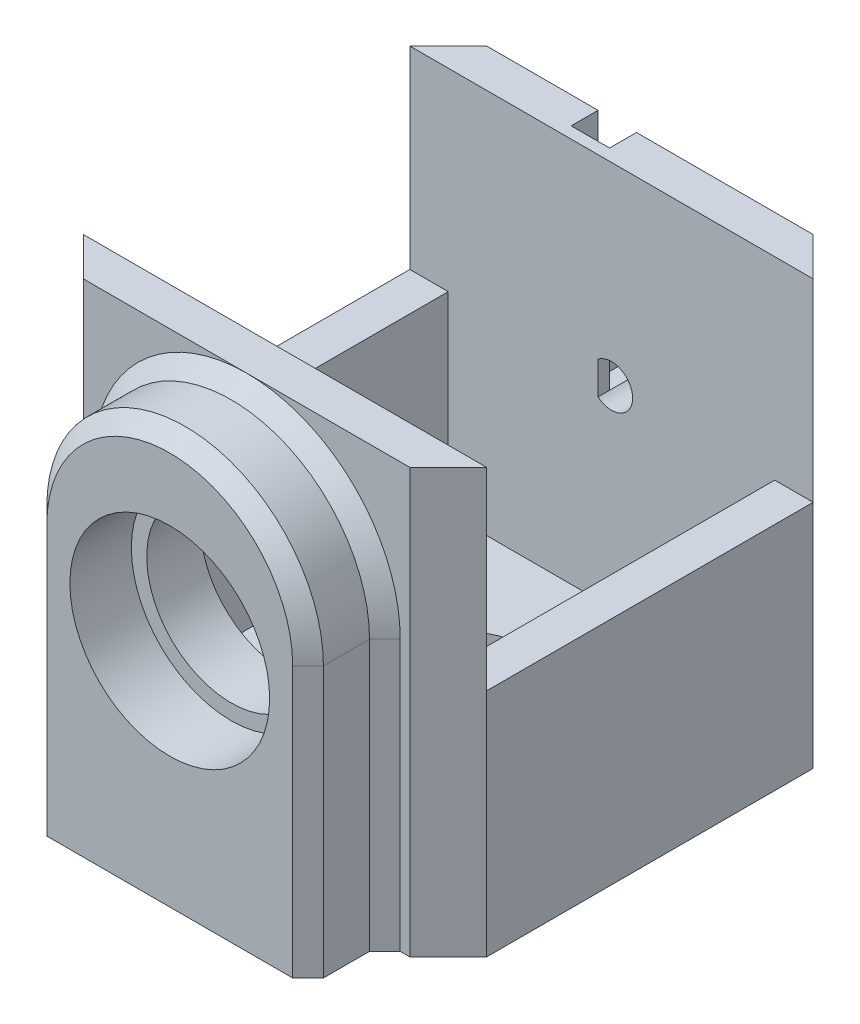
SolidWorks part; units mm, degrees
ref_plane "Front Plane" through (0, 0, 0) normal (0, 0, 1) x (1, 0, 0)
ref_plane "Top Plane" through (0, 0, 0) normal (0, 1, 0) x (1, 0, 0)
ref_plane "Right Plane" through (0, 0, 0) normal (1, 0, 0) x (0, 0, -1)
sketch "Sketch1" plane through (0, 0, 0) normal (0, 1, 0) x (1, 0, 0)
  line L0 (-26.25, 26.25) -> (-26.25, -26.25)
  line L1 (-21.25, 21.25) -> (21.25, 21.25)
  line L2 (-21.25, 21.25) -> (-21.25, -21.25)
  line L3 (-21.25, -21.25) -> (21.25, -21.25)
  line L4 (21.25, 21.25) -> (21.25, -21.25)
  line L5 (-21.25, 21.25) -> (21.25, -21.25) construction
  line L6 (-21.25, -21.25) -> (21.25, 21.25) construction
  line L7 (-26.25, -26.25) -> (26.25, -26.25)
  line L8 (26.25, 26.25) -> (26.25, -26.25)
  line L9 (-26.25, 26.25) -> (26.25, 26.25)
  point P0 (0, 0)
  dimension "D1" = 42.5
  dimension "D2" = 42.5
  dimension "D3" = 5
extrude "Boss-Extrude1" add sketch "Sketch1" along normal blind 60
sketch "Sketch2" plane through (0, 0, 0) normal (0, 1, 0) x (1, 0, 0)
  line L1 (-21.25, -21.25) -> (21.25, -21.25)
  line L2 (-21.25, -21.25) -> (-21.25, 21.25)
  line L3 (-21.25, 21.25) -> (21.25, 21.25)
  line L4 (21.25, -21.25) -> (21.25, 21.25)
  line L5 (-21.25, -21.25) -> (21.25, 21.25) construction
  line L6 (-21.25, 21.25) -> (21.25, -21.25) construction
  point P0 (0, 0)
extrude "Boss-Extrude2" add sketch "Sketch2" along normal blind 5
sketch "Sketch3" plane through (0, 5, 0) normal (0, 1, 0) x (1, 0, 0)
  line L0 (0, 21.25) -> (0, -21.25) construction
  line L1 (21.25, 21.25) -> (-21.25, 21.25) construction
  line L2 (-21.25, -21.25) -> (21.25, -21.25) construction
  line L3 (-21.25, 0) -> (21.25, 0) construction
  line L4 (-21.25, 21.25) -> (-21.25, -21.25) construction
  line L5 (21.25, -21.25) -> (21.25, 21.25) construction
  circle A0 centre (-15.5, 15.5) radius 1.75
  circle A1 centre (-15.5, -15.5) radius 1.75
  circle A2 centre (15.5, 15.5) radius 1.75
  circle A3 centre (15.5, -15.5) radius 1.75
  circle A4 centre (0, 0) radius 7.5
  dimension "D1" = 3.5
  dimension "D2" = 15
  dimension "D3" = 31
  dimension "D4" = 31
extrude "Cut-Extrude1" cut sketch "Sketch3" against normal through all both and the other way through all
sketch "Sketch4" plane through (0, 5, 0) normal (0, 1, 0) x (1, 0, 0)
  circle A0 centre (0, 0) radius 11.5
extrude "Cut-Extrude2" cut sketch "Sketch4" against normal blind 2
sketch "Sketch5" plane through (0, 0, -26.25) normal (0, 0, -1) x (-1, 0, 0)
  line L0 (0, 30) -> (0, -2.8991) construction
  line L1 (10, 30) -> (10, -2.8991)
  line L2 (-10, 30) -> (-10, -2.8991)
  line L3 (-26.25, 0) -> (26.25, 0) construction
  line L4 (0, 30) -> (26.25, 30) construction
  arc A0 (10, 30) -> (-10, 30) centre (0, 30) ccw
  arc A1 (-10, -2.8991) -> (10, -2.8991) centre (0, -2.8991) ccw
  circle A2 centre (-4, 37) radius 0.75
  circle A3 centre (0, 37) radius 0.75
  circle A4 centre (4, 37) radius 0.75
  circle A5 centre (-7, 34) radius 0.75
  circle A6 centre (-7, 30) radius 0.75
  circle A7 centre (-7, 26) radius 0.75
  circle A8 centre (-4, 23) radius 0.75
  circle A9 centre (0, 23) radius 0.75
  circle A10 centre (4, 23) radius 0.75
  circle A11 centre (7, 26) radius 0.75
  circle A12 centre (7, 30) radius 0.75
  circle A13 centre (7, 34) radius 0.75
  circle A14 centre (0, 30) radius 3.5
  point P3 (0, 13.5505)
  dimension "D1" = 10
  dimension "D3" = 1.5
  dimension "D6" = 4
  dimension "D10" = 7
  dimension "D2" = 30
  dimension "D4" = 4
  dimension "D5" = 4
  dimension "D7" = 4
  dimension "D8" = 7
  dimension "D9" = 7
extrude "Boss-Extrude3" add sketch "Sketch5" along normal blind 10
sketch "Sketch6" plane through (0, 0, -26.25) normal (0, 0, -1) x (-1, 0, 0)
  line L0 (-26.25, 0) -> (26.25, 0)
  line L1 (26.25, 0) -> (26.25, -16.2161)
  line L2 (26.25, -16.2161) -> (-26.25, -16.2161)
  line L3 (-26.25, -16.2161) -> (-26.25, 0)
extrude "Cut-Extrude3" cut sketch "Sketch6" against normal through all both and the other way through all
sketch "Sketch7" plane through (0, 0, -26.25) normal (0, 0, -1) x (-1, 0, 0)
  circle A0 centre (0, 30) radius 3.5
  circle A1 centre (-4, 37) radius 0.75
  circle A2 centre (0, 37) radius 0.75
  circle A3 centre (4, 37) radius 0.75
  circle A4 centre (7, 34) radius 0.75
  circle A5 centre (7, 30) radius 0.75
  circle A6 centre (7, 26) radius 0.75
  circle A7 centre (4, 23) radius 0.75
  circle A8 centre (0, 23) radius 0.75
  circle A9 centre (-4, 23) radius 0.75
  circle A10 centre (-7, 26) radius 0.75
  circle A11 centre (-7, 30) radius 0.75
  circle A12 centre (-7, 34) radius 0.75
  circle A13 centre (0, 37) radius 0.75 construction
  circle A14 centre (4, 37) radius 0.75 construction
  circle A15 centre (-4, 37) radius 0.75 construction
  circle A16 centre (-7, 34) radius 0.75 construction
  circle A17 centre (-7, 30) radius 0.75 construction
  circle A18 centre (-7, 26) radius 0.75 construction
  circle A19 centre (-4, 23) radius 0.75 construction
  circle A20 centre (0, 23) radius 0.75 construction
  circle A21 centre (4, 23) radius 0.75 construction
  circle A22 centre (7, 26) radius 0.75 construction
  circle A23 centre (7, 30) radius 0.75 construction
  circle A24 centre (7, 34) radius 0.75 construction
  circle A25 centre (0, 30) radius 3.5 construction
extrude "Cut-Extrude4" cut sketch "Sketch7" against normal blind 23
chamfer "Chamfer1" distance 5 angle 45 7 edges at (26.25, 30, 26.25) (-26.25, 30, 26.25) (26.25, 30, -26.25) (-26.25, 30, -26.25) (-10, 15, -36.25) (10, 15, -36.25) (0, 40, -36.25)
chamfer "Chamfer3" distance 2 angle 45 4 edges at (-21.25, 60, 0) (0, 60, 21.25) (0, 60, -21.25) (21.25, 60, 0)
chamfer "Chamfer4" distance 1 angle 45 2 edges at (3.5, 30, -21.25) (-3.5, 30, -36.25)
sketch "Sketch8" plane through (0, 0, 26.25) normal (0, 0, 1) x (1, 0, 0)
  line L0 (0, 35.1901) -> (0, 0) construction
  line L3 (18, 35.1901) -> (18, 0)
  line L4 (-18, 35.1901) -> (-18, 0)
  line L7 (-18, 0) -> (18, 0)
  arc A3 (18, 35.1901) -> (-18, 35.1901) centre (0, 35.1901) ccw
  circle A5 centre (0, 35.1901) radius 13
  point P3 (0, 7.685)
extrude "Boss-Extrude4" add sketch "Sketch8" along normal blind 10
sketch "Sketch9" plane through (0, 0, 26.25) normal (0, 0, 1) x (1, 0, 0)
  circle A0 centre (0, 35.1901) radius 12
  circle A1 centre (0, 35.1901) radius 13 construction
extrude "Cut-Extrude5" cut sketch "Sketch9" against normal blind 10
chamfer "Chamfer5" distance 2 angle 45 6 edges at (18, 17.5951, 26.25) (-18, 17.5951, 26.25) (0, 53.1901, 26.25) (18, 17.5951, 36.25) (-18, 17.5951, 36.25) (0, 53.1901, 36.25)
sketch "Sketch10" plane through (-21.25, 0, 0) normal (1, 0, 0) x (0, 0, -1)
  line L0 (-21.25, 0) -> (21.25, 0) construction
  line L1 (-21.25, 75.699) -> (21.25, 75.699)
  line L2 (-21.25, 75.699) -> (-21.25, 30)
  line L3 (-21.25, 30) -> (21.25, 30)
  line L4 (21.25, 75.699) -> (21.25, 30)
  line L5 (-21.25, 75.699) -> (21.25, 30) construction
  line L6 (-21.25, 30) -> (21.25, 75.699) construction
  point P0 (0, 52.8495)
  dimension "D1" = 30
  dimension "D2" = 42.5
extrude "Cut-Extrude6" cut sketch "Sketch10" against normal through all both and the other way through all
sketch "Sketch11" plane through (0, 0, 36.25) normal (0, 0, 1) x (1, 0, 0)
  circle A0 centre (0, 30) radius 13
  circle A1 centre (0, 30) radius 3.5 construction
  dimension "D1" = 26
extrude "Cut-Extrude7" cut sketch "Sketch11" against normal up to surface (10 mm away) up to face at (12, 35.1901, 26.25)
sketch "Sketch12" plane through (0, 0, 36.25) normal (0, 0, 1) x (1, 0, 0)
  line L0 (0, 37) -> (0, 8.7788) construction
  line L1 (13.7424, 37) -> (13.7424, 8.7788)
  line L2 (-13.7424, 37) -> (-13.7424, 8.7788)
  circle A2 centre (0, 30) radius 13
  arc A3 (13.7424, 37) -> (-13.7424, 37) centre (0, 37) ccw
  arc A4 (-13.7424, 8.7788) -> (13.7424, 8.7788) centre (0, 8.7788) ccw
  point P3 (0, 22.8894)
  dimension "D1" = 26
extrude "Boss-Extrude6" add sketch "Sketch12" against normal up to surface (15 mm away) up to face at (-12, 35.1901, 21.25)
sketch "Sketch13" plane through (0, 0, 36.25) normal (0, 0, 1) x (1, 0, 0)
  circle A0 centre (0, 30) radius 13
  circle A1 centre (0, 30) radius 13 construction
extrude "Boss-Extrude7" add sketch "Sketch13" along normal blind 7 from surface starting at face at (0, 40.5, 21.25)
sketch "Sketch14" plane through (0, 0, 28.25) normal (0, 0, 1) x (1, 0, 0)
  circle A0 centre (0, 30) radius 11
  circle A1 centre (0, 30) radius 13 construction
  dimension "D1" = 22
extrude "Cut-Extrude8" cut sketch "Sketch14" against normal blind 14
sketch "Sketch15" plane through (0, 0, 0) normal (0, -1, 0) x (1, 0, 0)
  line L1 (-34.0759, -81.0818) -> (34.0759, -81.0818)
  line L2 (-34.0759, -81.0818) -> (-34.0759, 81.0818)
  line L3 (-34.0759, 81.0818) -> (34.0759, 81.0818)
  line L4 (34.0759, -81.0818) -> (34.0759, 81.0818)
  line L5 (-34.0759, -81.0818) -> (34.0759, 81.0818) construction
  line L6 (-34.0759, 81.0818) -> (34.0759, -81.0818) construction
  point P0 (0, 0)
extrude "Cut-Extrude9" cut sketch "Sketch15" along normal blind 34
sketch "Sketch16" plane through (0, 0, -36.25) normal (0, 0, -1) x (-1, 0, 0)
  circle A0 centre (0, 30) radius 12
  circle A1 centre (0, 30) radius 2.75
  dimension "D1" = 5.5
extrude "Boss-Extrude8" add sketch "Sketch16" against normal up to surface (15 mm away) up to face at (-6.25, 30, -21.25)
sketch "Sketch17" plane through (0, 0, -36.25) normal (0, 0, -1) x (-1, 0, 0)
  line L1 (1.75, 32.1213) -> (1.75, 27.8787)
  arc A3 (1.75, 27.8787) -> (1.75, 32.1213) centre (0, 30) ccw
  dimension "D1" = 1.75
extrude "Boss-Extrude9" add sketch "Sketch17" against normal up to surface (15 mm away) up to face at (0, 40.5, -21.25)
chamfer "Chamfer6" distance 3 angle 45 1 edges at (0, 42, -36.25)
sketch "Sketch18" plane through (0, 0, 0) normal (1, 0, 0) x (0, 0, -1)
  line L1 (-40.1909, 65.684) -> (40.1909, 65.684)
  line L2 (-40.1909, 65.684) -> (-40.1909, 55.1901)
  line L3 (-40.1909, 55.1901) -> (40.1909, 55.1901)
  line L4 (40.1909, 65.684) -> (40.1909, 55.1901)
  line L5 (-40.1909, 65.684) -> (40.1909, 55.1901) construction
  line L6 (-40.1909, 55.1901) -> (40.1909, 65.684) construction
  point P0 (0, 60.4371)
extrude "Cut-Extrude10" cut sketch "Sketch18" against normal through all both and the other way through all
sketch "Sketch19" plane through (-1.75, 0, 0) normal (1, 0, 0) x (0, 0, -1)
  line L0 (36.25, 22.5167) -> (36.25, 39) construction
  line L1 (31.25, 34.9075) -> (27, 32.4537)
  line L2 (27, 32.4537) -> (27, 27.5463)
  line L3 (27, 27.5463) -> (31.25, 25.0925)
  line L4 (31.25, 25.0925) -> (35.5, 27.5463)
  line L5 (35.5, 27.5463) -> (35.5, 32.4537)
  line L6 (35.5, 32.4537) -> (31.25, 34.9075)
  line L7 (36.25, 32.1213) -> (36.25, 27.8787) construction
  circle A0 centre (31.25, 30) radius 4.25 construction
  circle A1 centre (31.25, 30) radius 2.75
  point P13 (36.25, 30)
  line M7 (36.25, 32.1213) -> (21.25, 32.1213)
  line M9 (21.25, 27.8787) -> (36.25, 27.8787)
  dimension "D1" = 8.5
  dimension "D2" = 5
extrude "Cut-Extrude11" cut sketch "Sketch19" against normal blind 5
sketch "Sketch20" plane through (0, 0, 0) normal (0, 1, 0) x (1, 0, 0)
  line L1 (-6.75, 22.75) -> (-1.75, 22.75)
  line L2 (-6.75, 22.75) -> (-6.75, 31.25)
  line L3 (-6.75, 31.25) -> (-1.75, 31.25)
  line L4 (-1.75, 22.75) -> (-1.75, 31.25)
  line L5 (-6.75, 22.75) -> (-1.75, 31.25) construction
  line L6 (-6.75, 31.25) -> (-1.75, 22.75) construction
  point P0 (-4.25, 27)
  dimension "D1" = 5
  dimension "D2" = 0
  dimension "D3" = 5
  dimension "D4" = 8.5
extrude "Cut-Extrude12" cut sketch "Sketch20" along normal through all from offset 25
extrude "Cut-Extrude13" cut sketch "Sketch19<2>" against normal through all contours A1 M7 M9 | A1 M7 | A1 M9 region at (-1.75, 30, -31.25) region at (-1.75, 32.3754, -31.25) region at (-1.75, 27.6246, -31.25)
sketch "Sketch19<2>" plane through (-1.75, 0, 0) normal (1, 0, 0) x (0, 0, -1) same geometry as "Sketch19"
sketch "Sketch21" plane through (0, 0, 0) normal (1, 0, 0) x (0, 0, -1)
  circle A0 centre (31.25, 30) radius 4.5
  arc A1 (33.25, 31.8875) -> (33.25, 28.1125) centre (31.25, 30) ccw construction
  dimension "D1" = 9
extrude "Cut-Extrude15" cut sketch "Sketch21" against normal blind 15 from offset 10 offset against normal yes
